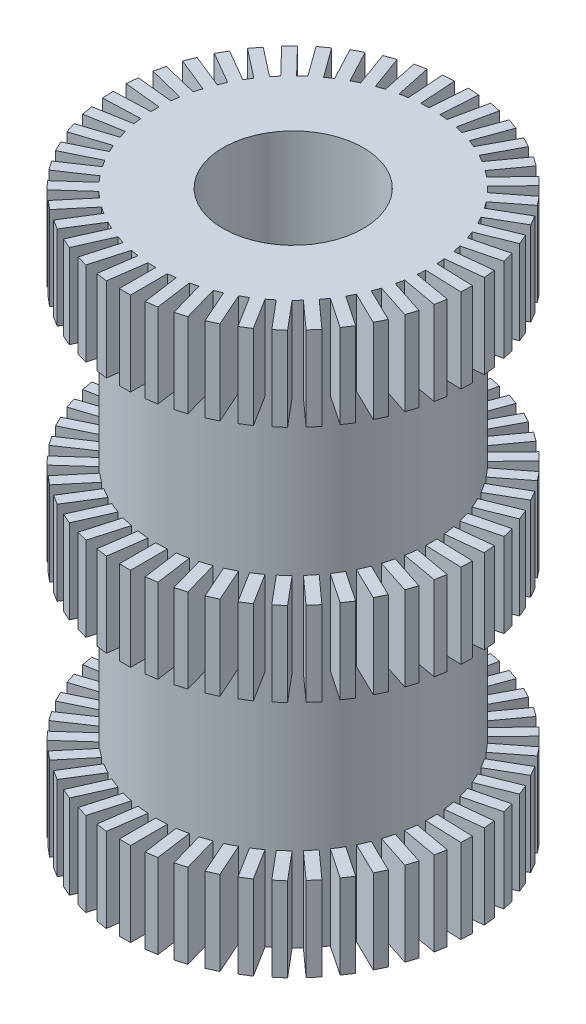
SolidWorks part; units mm, degrees
material "Brass"
ref_plane "Front Plane" through (0, 0, 0) normal (0, 0, 1) x (1, 0, 0)
ref_plane "Top Plane" through (0, 0, 0) normal (0, 1, 0) x (1, 0, 0)
ref_plane "Right Plane" through (0, 0, 0) normal (1, 0, 0) x (0, 0, -1)
sketch "Sketch1" plane through (0, 0, 0) normal (0, 1, 0) x (1, 0, 0)
  circle A0 centre (0, 0) radius 2.45
  dimension "D1" = 4.9
extrude "Boss-Extrude1" add sketch "Sketch1" along normal blind 10
hole_wizard "M3x0.5 Tapped Hole1" positions "Sketch2" profile "Sketch3" tap size "M3x0.5" standard "ANSI Metric" end condition through all
sketch "Sketch2" plane through (0, 10, 0) normal (0, 1, 0) x (1, 0, 0)
  point P0 (0, 0)
sketch "Sketch3" plane through (0, 10, 0) normal (1, 0, 0) x (0, 0, 1)
  line L0 (0, 0) -> (0, 10)
  line L1 (0, 10) -> (1.25, 10)
  line L2 (1.25, 10) -> (1.25, 0)
  line L5 (1.25, 0) -> (0, 0)
  line L11 (0, -6.35) -> (0, 107.95) construction
  dimension "Thru Tap Drill Dia." = 2.5
  dimension "Thru Tap Drill Depth" = 10
cosmetic thread "Hole Thread1" parameters "D2"=3
ref_plane "Plane1" through (0, 0, 3) normal (0, 0, 1) x (1, 0, 0)
sketch "Sketch4" plane through (0, 0, 3) normal (0, 0, 1) x (1, 0, 0)
  line L0 (2.45, 10) -> (-2.45, 10) construction
  line L1 (0.2, 10) -> (0, 10)
  line L2 (0.2, 10) -> (0.2, 8.5)
  line L3 (0.2, 8.5) -> (0, 8.5)
  line L4 (0, 10) -> (0, 8.5)
  line L5 (0, -2.695) -> (0, 2.695) construction
  line L7 (0, 0) -> (0.2, 0)
  line L8 (0, 0) -> (0, 1.5)
  line L9 (0, 1.5) -> (0.2, 1.5)
  line L10 (0.2, 0) -> (0.2, 1.5)
  line L11 (0, 5.75) -> (0.2, 5.75)
  line L12 (0, 5.75) -> (0, 4.25)
  line L13 (0, 4.25) -> (0.2, 4.25)
  line L14 (0.2, 5.75) -> (0.2, 4.25)
  point P17 (0, 5)
  dimension "D1" = 0.2
  dimension "D2" = 1.5
  dimension "D3" = 1.5
  dimension "D4" = 0.2
  dimension "D5" = 1.5
  dimension "D6" = 5
extrude "Boss-Extrude2" add sketch "Sketch4" along normal blind 0.1 and the other way up to surface other way up to face at (0, 10, 2.45)
pattern_circular "CirPattern1" count 45 over 360 about axis through (0, 10, 0) along (0, 1, 0) of "Boss-Extrude2"
